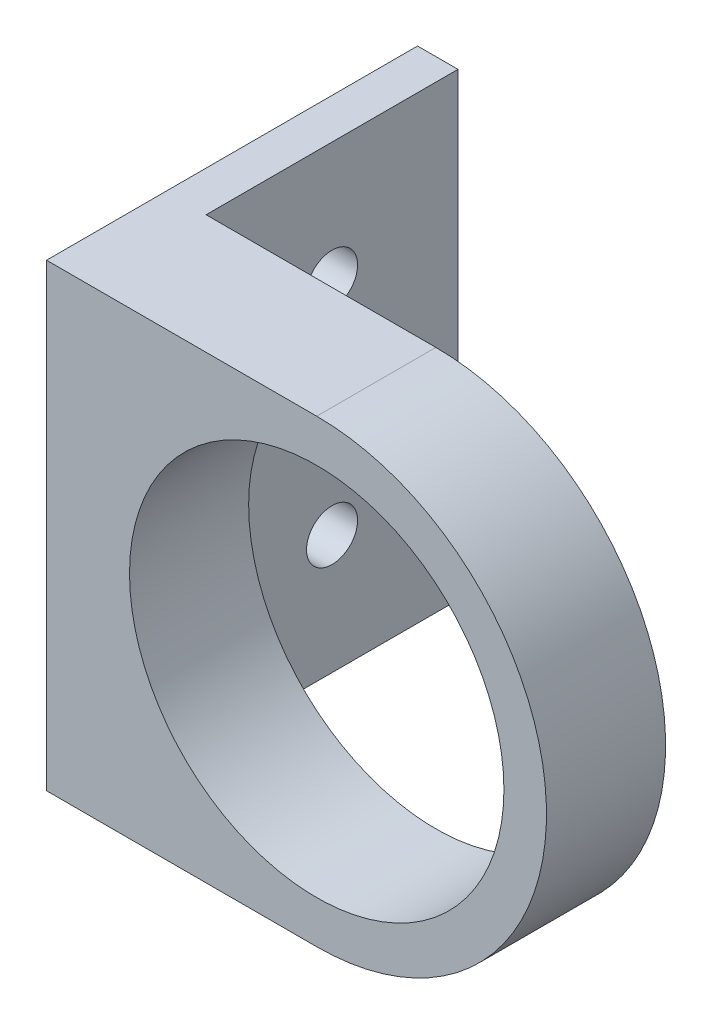
SolidWorks part; units mm, degrees
ref_plane "Front Plane" through (0, 0, 0) normal (0, 0, 1) x (1, 0, 0)
ref_plane "Top Plane" through (0, 0, 0) normal (0, 1, 0) x (1, 0, 0)
ref_plane "Right Plane" through (0, 0, 0) normal (1, 0, 0) x (0, 0, -1)
sketch "Sketch1" plane through (0, 0, 0) normal (0, 0, 1) x (1, 0, 0)
  line L0 (0, 13.5) -> (-15.875, 13.5)
  line L1 (-15.875, 13.5) -> (-15.875, -13.5)
  line L2 (-15.875, -13.5) -> (0, -13.5)
  circle A0 centre (0, 0) radius 11
  circle A1 centre (0, 0) radius 13.5
  arc A2 (0, 13.5) -> (0, -13.5) centre (0, 0) ccw
  dimension "D1" = 22
  dimension "D2" = 27
  dimension "D3" = 4.875
extrude "Boss-Extrude1" add sketch "Sketch1" along normal blind 7 contours A1 L0 L1 L2 | A1 A0 region at (-13.8132, 0, 0) region at (9.2759, 9.2759, 0)
sketch "Sketch3" plane through (0, 0, 0) normal (0, 0, -1) x (-1, 0, 0)
  line L2 (13.5, 0) -> (13.5, 13.5)
  line L3 (0, 13.5) -> (15.875, 13.5) construction
  line L4 (13.5, 13.5) -> (15.875, 13.5)
  line L5 (15.875, 13.5) -> (15.875, -13.5)
  line L6 (15.875, -13.5) -> (13.5, -13.5)
  line L7 (15.875, -13.5) -> (0, -13.5) construction
  line L8 (13.5, -13.5) -> (13.5, 0)
extrude "Boss-Extrude2" add sketch "Sketch3" along normal blind 14.8
sketch "Sketch4" plane through (-13.5, 0, 0) normal (1, 0, 0) x (0, 0, -1)
  line L0 (14.8, 13.5) -> (0, 13.5) construction
  line L3 (14.8, -13.5) -> (0, -13.5) construction
  circle A0 centre (7.4, 6.5) radius 1.5
  circle A1 centre (7.4, -6.5) radius 1.5
  dimension "D1" = 3
  dimension "D2" = 3
  dimension "D4" = 7
  dimension "D3" = 7
extrude "Cut-Extrude1" cut sketch "Sketch4" against normal blind 4.8
